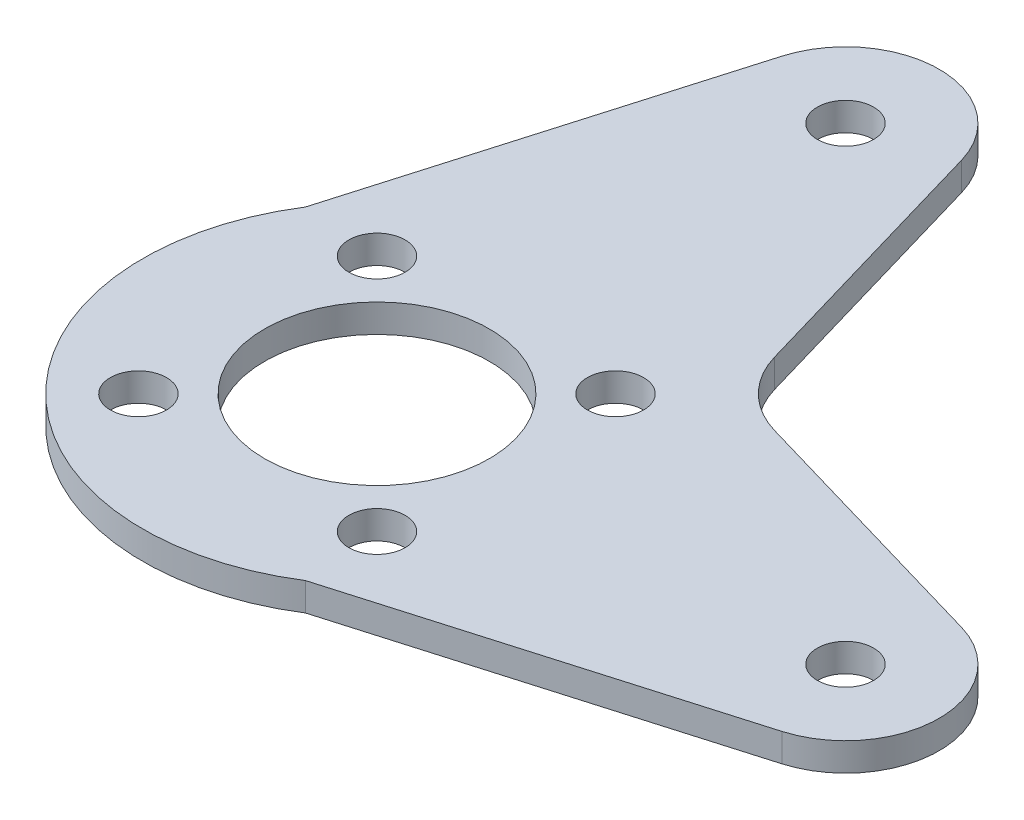
SolidWorks part; units mm, degrees
material "201 Stal nierdzewna odprężona (SS)"
ref_plane "Płaszczyzna przednia" through (0, 0, 0) normal (0, 0, 1) x (1, 0, 0)
ref_plane "Płaszczyzna górna" through (0, 0, 0) normal (0, 1, 0) x (1, 0, 0)
ref_plane "Płaszczyzna prawa" through (0, 0, 0) normal (1, 0, 0) x (0, 0, -1)
sketch "Szkic1" plane through (0, 0, 0) normal (0, 1, 0) x (1, 0, 0)
  line L0 (13.44, -21.08) -> (52.8, -9.6)
  line L1 (24.6194, 17.8194) -> (52.8, 9.6)
  line L2 (17.8194, 24.6194) -> (9.6, 52.8)
  line L3 (-21.08, 13.44) -> (-9.6, 52.8)
  arc A0 (52.8, -9.6) -> (52.8, 9.6) centre (50, 0) ccw
  arc A1 (17.8194, 24.6194) -> (24.6194, 17.8194) centre (27.4194, 27.4194) ccw
  arc A2 (9.6, 52.8) -> (-9.6, 52.8) centre (0, 50) ccw
  circle A3 centre (0, 50) radius 3
  circle A4 centre (-12.7279, 12.7279) radius 3
  circle A5 centre (-12.7279, -12.7279) radius 3
  circle A6 centre (12.7279, -12.7279) radius 3
  circle A7 centre (12.7279, 12.7279) radius 3
  circle A8 centre (50, 0) radius 3
  arc A23 (-21.08, 13.44) -> (13.44, -21.08) centre (0, 0) ccw
  circle A24 centre (0, 0) radius 12
extrude "Dodanie-wyciągnięcie1" add sketch "Szkic1" along normal blind 3
